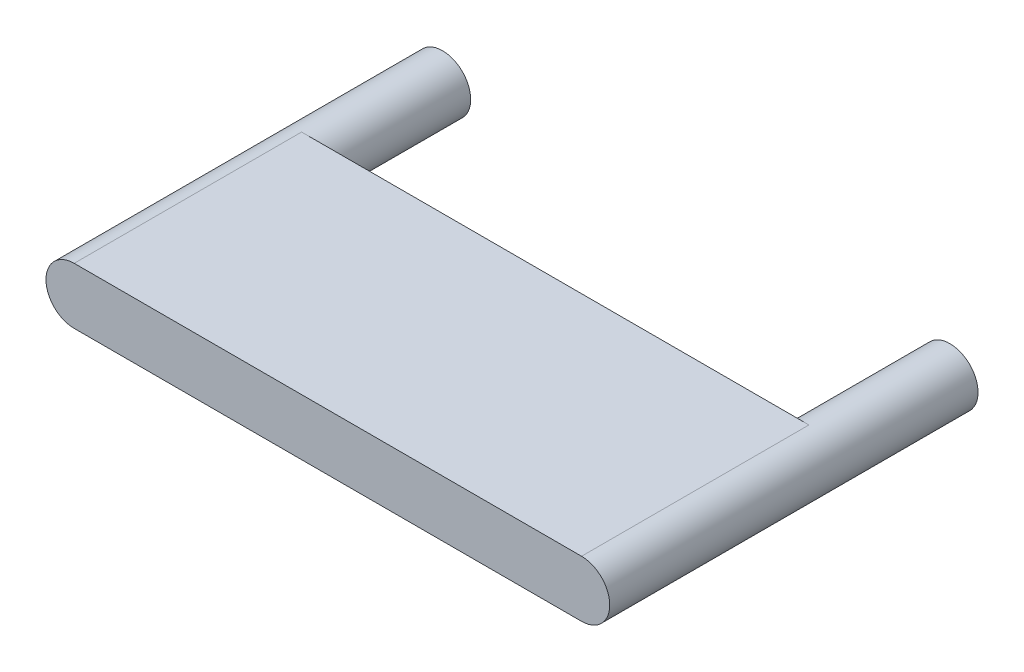
SolidWorks part; units mm, degrees
ref_plane "Front Plane" through (0, 0, 0) normal (0, 0, 1) x (1, 0, 0)
ref_plane "Top Plane" through (0, 0, 0) normal (0, 1, 0) x (1, 0, 0)
ref_plane "Right Plane" through (0, 0, 0) normal (1, 0, 0) x (0, 0, -1)
sketch "Sketch1" plane through (0, 0, 0) normal (0, 1, 0) x (1, 0, 0)
  line L1 (25.4, -12.7) -> (-25.4, -12.7)
  line L2 (25.4, -12.7) -> (25.4, 12.7)
  line L3 (25.4, 12.7) -> (-25.4, 12.7)
  line L4 (-25.4, -12.7) -> (-25.4, 12.7)
  line L5 (25.4, -12.7) -> (-25.4, 12.7) construction
  line L6 (25.4, 12.7) -> (-25.4, -12.7) construction
  point P0 (0, 0)
  dimension "D1" = 50.8
  dimension "D2" = 25.4
extrude "Boss-Extrude1" add sketch "Sketch1" along normal blind 5.08
fillet "Fillet2" 2 edges at (-25.4, 5.08, 0) (-25.4, 0, 0) type full round first side face at (0, 5.08, 0) second side face at (0, 0, 0) middle face at (-25.4, 2.54, 0)
fillet "Fillet3" 2 edges at (25.4, 5.08, 0) (25.4, 0, 0) type full round first side face at (1.27, 5.08, 0) second side face at (1.27, 0, 0) middle face at (25.4, 2.54, 0)
sketch "Sketch2" plane through (0, 0, -12.7) normal (0, 0, -1) x (-1, 0, 0)
  circle A0 centre (-22.86, 2.54) radius 2.54
extrude "Boss-Extrude2" add sketch "Sketch2" along normal blind 12.7
sketch "Sketch3" plane through (0, 0, -12.7) normal (0, 0, -1) x (-1, 0, 0)
  circle A0 centre (22.86, 2.54) radius 2.54
extrude "Boss-Extrude3" add sketch "Sketch3" along normal blind 12.7
sketch "Sketch4" plane through (0, 0, 0) normal (0, -1, 0) x (-1, 0, 0)
  line L0 (22.86, -12.7) -> (-22.86, -12.7) construction
  line L2 (26.4385, -17.6094) -> (-26.4385, -17.6094)
  line L3 (26.4385, -17.6094) -> (26.4385, -7.7906)
  line L4 (26.4385, -7.7906) -> (-26.4385, -7.7906)
  line L5 (-26.4385, -17.6094) -> (-26.4385, -7.7906)
  line L6 (26.4385, -17.6094) -> (-26.4385, -7.7906) construction
  line L7 (26.4385, -7.7906) -> (-26.4385, -17.6094) construction
  point P2 (0, -12.7)
extrude "Cut-Extrude1" cut sketch "Sketch4" against normal blind 12.7
